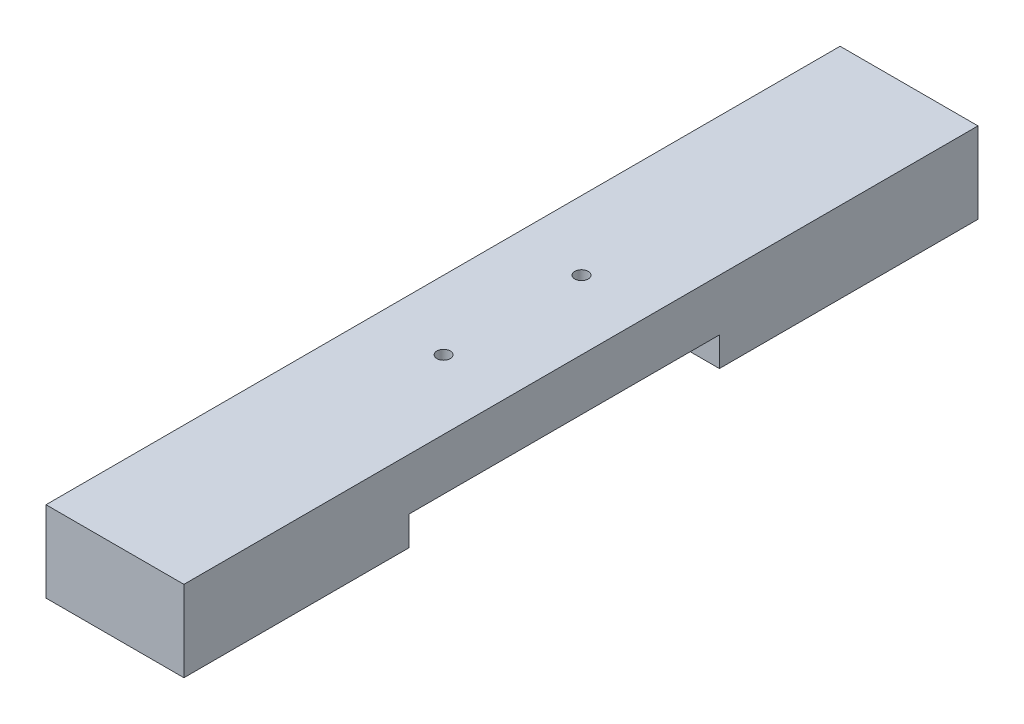
SolidWorks part; units mm, degrees
ref_plane "Front" through (0, 0, 0) normal (0, 0, 1) x (1, 0, 0)
ref_plane "Top" through (0, 0, 0) normal (0, 1, 0) x (1, 0, 0)
ref_plane "Right" through (0, 0, 0) normal (1, 0, 0) x (0, 0, -1)
sketch "Sketch1" plane through (0, 0, 0) normal (0, 0, 1) x (1, 0, 0)
  line L1 (0, 0) -> (101.6, 0)
  line L2 (0, 0) -> (0, 59.6)
  line L3 (0, 59.6) -> (101.6, 59.6)
  line L4 (101.6, 0) -> (101.6, 59.6)
  dimension "D1" = 59.6
  dimension "D2" = 101.6
extrude "Boss-Extrude1" add sketch "Sketch1" along normal blind 585.0001
sketch "Sketch2" plane through (0, 0, 0) normal (-1, 0, 0) x (0, 0, 1)
  line L0 (190.5, 0) -> (190.5, 21.5)
  line L1 (585.0001, 0) -> (0, 0) construction
  line L2 (190.5, 21.5) -> (419.1, 21.5)
  line L3 (419.1, 21.5) -> (419.1, 0)
  line L4 (419.1, 0) -> (190.5, 0)
  line L5 (0, 59.6) -> (0, 0) construction
  dimension "D1" = 190.5
  dimension "D2" = 21.5
  dimension "D3" = 228.6
extrude "Cut-Extrude1" cut sketch "Sketch2" against normal through all
sketch "Sketch5" plane through (0, 0, 0) normal (-1, 0, 0) x (0, 0, 1)
  arc A0 (6.7, 6.6) -> (13.3, 6.6) centre (10, 6.6) ccw construction
  arc A1 (13.3, 6.6) -> (6.7, 6.6) centre (10, 6.6) ccw construction
  arc A2 (6.7, 52.6) -> (13.3, 52.6) centre (10, 52.6) ccw construction
  arc A3 (13.3, 52.6) -> (6.7, 52.6) centre (10, 52.6) ccw construction
  arc A4 (6.7, 6.6) -> (13.3, 6.6) centre (10, 6.6) ccw
  arc A5 (13.3, 6.6) -> (6.7, 6.6) centre (10, 6.6) ccw
  arc A6 (6.7, 52.6) -> (13.3, 52.6) centre (10, 52.6) ccw
  arc A7 (13.3, 52.6) -> (6.7, 52.6) centre (10, 52.6) ccw
  arc A8 (170, 31.35) -> (170, 27.85) centre (170, 29.6) ccw construction
  arc A9 (170, 27.85) -> (170, 31.35) centre (170, 29.6) ccw construction
  arc A10 (110, 27.85) -> (110, 31.35) centre (110, 29.6) ccw construction
  arc A11 (110, 31.35) -> (110, 27.85) centre (110, 29.6) ccw construction
  arc A12 (50, 27.85) -> (50, 31.35) centre (50, 29.6) ccw construction
  arc A13 (50, 31.35) -> (50, 27.85) centre (50, 29.6) ccw construction
  arc A14 (170, 31.35) -> (170, 27.85) centre (170, 29.6) ccw
  arc A15 (170, 27.85) -> (170, 31.35) centre (170, 29.6) ccw
  arc A16 (110, 27.85) -> (110, 31.35) centre (110, 29.6) ccw
  arc A17 (110, 31.35) -> (110, 27.85) centre (110, 29.6) ccw
  arc A18 (50, 27.85) -> (50, 31.35) centre (50, 29.6) ccw
  arc A19 (50, 31.35) -> (50, 27.85) centre (50, 29.6) ccw
  arc A20 (530, 27.85) -> (530, 31.35) centre (530, 29.6) ccw construction
  arc A21 (530, 31.35) -> (530, 27.85) centre (530, 29.6) ccw construction
  arc A22 (470, 27.85) -> (470, 31.35) centre (470, 29.6) ccw construction
  arc A23 (470, 31.35) -> (470, 27.85) centre (470, 29.6) ccw construction
  arc A24 (410, 27.85) -> (410, 31.35) centre (410, 29.6) ccw construction
  arc A25 (410, 31.35) -> (410, 27.85) centre (410, 29.6) ccw construction
  arc A26 (350, 27.85) -> (350, 31.35) centre (350, 29.6) ccw construction
  arc A27 (350, 31.35) -> (350, 27.85) centre (350, 29.6) ccw construction
  arc A28 (290, 27.85) -> (290, 31.35) centre (290, 29.6) ccw construction
  arc A29 (290, 31.35) -> (290, 27.85) centre (290, 29.6) ccw construction
  arc A30 (230, 27.85) -> (230, 31.35) centre (230, 29.6) ccw construction
  arc A31 (230, 31.35) -> (230, 27.85) centre (230, 29.6) ccw construction
  arc A32 (530, 27.85) -> (530, 31.35) centre (530, 29.6) ccw
  arc A33 (530, 31.35) -> (530, 27.85) centre (530, 29.6) ccw
  arc A34 (470, 27.85) -> (470, 31.35) centre (470, 29.6) ccw
  arc A35 (470, 31.35) -> (470, 27.85) centre (470, 29.6) ccw
  arc A36 (410, 27.85) -> (410, 31.35) centre (410, 29.6) ccw
  arc A37 (410, 31.35) -> (410, 27.85) centre (410, 29.6) ccw
  arc A38 (350, 27.85) -> (350, 31.35) centre (350, 29.6) ccw
  arc A39 (350, 31.35) -> (350, 27.85) centre (350, 29.6) ccw
  arc A40 (290, 27.85) -> (290, 31.35) centre (290, 29.6) ccw
  arc A41 (290, 31.35) -> (290, 27.85) centre (290, 29.6) ccw
  arc A42 (230, 27.85) -> (230, 31.35) centre (230, 29.6) ccw
  arc A43 (230, 31.35) -> (230, 27.85) centre (230, 29.6) ccw
  arc A44 (582.3, 6.6) -> (575.7, 6.6) centre (579, 6.6) ccw construction
  arc A45 (575.7, 6.6) -> (582.3, 6.6) centre (579, 6.6) ccw construction
  arc A46 (562.7, 6.6) -> (569.3, 6.6) centre (566, 6.6) ccw construction
  arc A47 (569.3, 6.6) -> (562.7, 6.6) centre (566, 6.6) ccw construction
  arc A48 (575.7, 52.6) -> (582.3, 52.6) centre (579, 52.6) ccw construction
  arc A49 (582.3, 52.6) -> (575.7, 52.6) centre (579, 52.6) ccw construction
  arc A50 (562.7, 52.6) -> (569.3, 52.6) centre (566, 52.6) ccw construction
  arc A51 (569.3, 52.6) -> (562.7, 52.6) centre (566, 52.6) ccw construction
  arc A52 (582.3, 6.6) -> (575.7, 6.6) centre (579, 6.6) ccw
  arc A53 (575.7, 6.6) -> (582.3, 6.6) centre (579, 6.6) ccw
  arc A54 (562.7, 6.6) -> (569.3, 6.6) centre (566, 6.6) ccw
  arc A55 (569.3, 6.6) -> (562.7, 6.6) centre (566, 6.6) ccw
  arc A56 (575.7, 52.6) -> (582.3, 52.6) centre (579, 52.6) ccw
  arc A57 (582.3, 52.6) -> (575.7, 52.6) centre (579, 52.6) ccw
  arc A58 (562.7, 52.6) -> (569.3, 52.6) centre (566, 52.6) ccw
  arc A59 (569.3, 52.6) -> (562.7, 52.6) centre (566, 52.6) ccw
extrude "Cut-Extrude4" cut sketch "Sketch5" against normal blind 6.35 from surface contours A32 A33 | A34 A35 | A36 A37 | A38 A39 | A40 A41 | A42 A43 | A15 A14 | A16 A17 | A18 A19 starting at face at (0, 20.275, 298.65)
extrude "Cut-Extrude5" cut sketch "Sketch5<3>" against normal blind 25.4 from surface contours A54 A55 | A52 A53 | A56 A57 | A58 A59 | A4 A5 | A6 A7 region at (0, 6.6, 10) region at (0, 52.6, 10) region at (0, 6.6, 579) region at (0, 6.6, 566) region at (0, 52.6, 579) region at (0, 52.6, 566) starting at face at (0, 29.6, 528.25)
sketch "Sketch5<3>" plane through (0, 0, 0) normal (-1, 0, 0) x (0, 0, 1) same geometry as "Sketch5"
sketch "Sketch6" plane through (0, 21.5, 0) normal (0, -1, 0) x (1, 0, 0)
  circle A0 centre (50.8, 342.9) radius 4.9344 construction
  circle A1 centre (50.8, 241.3) radius 4.9344 construction
  circle A2 centre (50.8, 342.9) radius 4.9344
  circle A3 centre (50.8, 241.3) radius 4.9344
extrude "Cut-Extrude6" cut sketch "Sketch6" against normal through all
